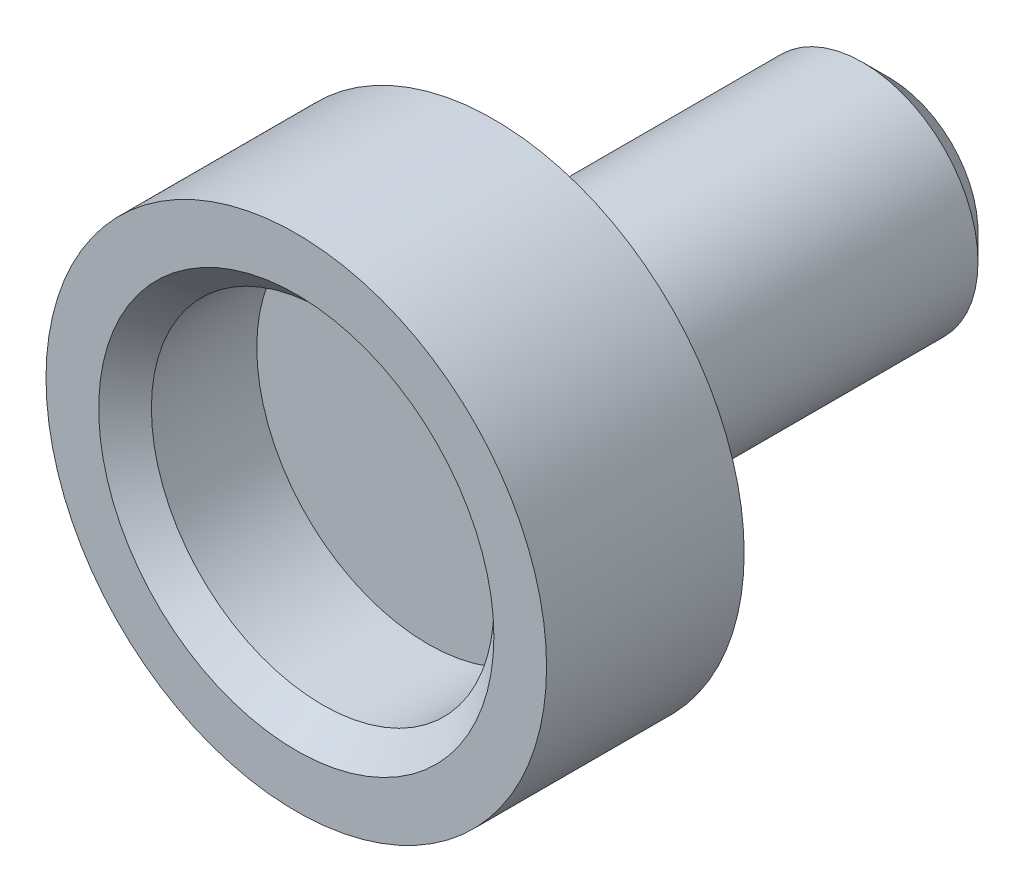
SolidWorks part; units mm, degrees
ref_plane "Plan de face" through (0, 0, 0) normal (0, 0, 1) x (1, 0, 0)
ref_plane "Plan de dessus" through (0, 0, 0) normal (0, 1, 0) x (1, 0, 0)
ref_plane "Plan de droite" through (0, 0, 0) normal (1, 0, 0) x (0, 0, -1)
sketch "Esquisse1" plane through (0, 0, 0) normal (0, 0, 1) x (1, 0, 0)
  circle A0 centre (0, 0) radius 2.6
  circle A1 centre (0, 0) radius 3.8
  dimension "D1" = 5.2
  dimension "D2" = 1.2
extrude "Boss.-Extru.1" add sketch "Esquisse1" along normal blind 2
sketch "Esquisse2" plane through (0, 0, 0) normal (0, 0, -1) x (-1, 0, 0)
  circle A1 centre (0, 0) radius 3.8
  circle A2 centre (0, 0) radius 3.8
  dimension "D1" = 0
extrude "Boss.-Extru.2" add sketch "Esquisse2" along normal blind 1
sketch "Esquisse3" plane through (0, 0, -1) normal (0, 0, -1) x (-1, 0, 0)
  circle A0 centre (0, 0) radius 1.75
  dimension "D1" = 3.5
extrude "Boss.-Extru.3" add sketch "Esquisse3" along normal blind 6
fillet "Congé1" radius 0.6 1 edges at (-1.75, 0, -1)
chamfer "Chanfrein1" distance 0.4 angle 45 1 edges at (-1.75, 0, -7)
chamfer "Chanfrein2" distance 0.4 angle 45 1 edges at (2.6, 0, 2)
